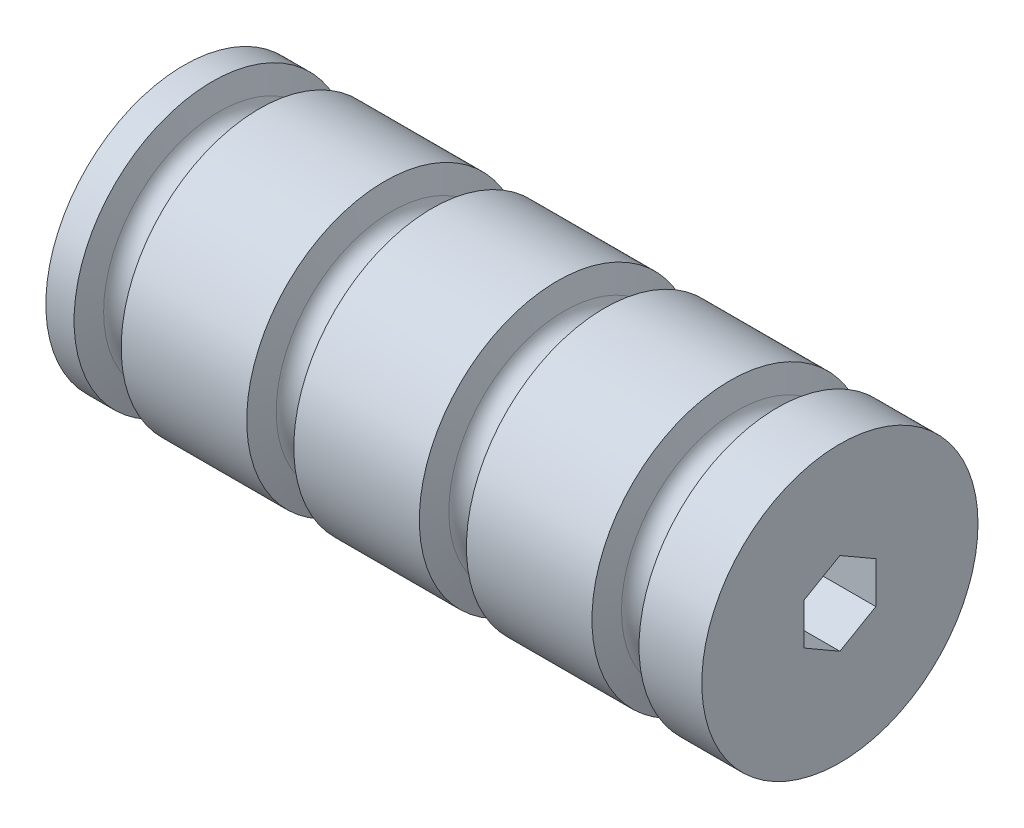
SolidWorks part; units mm, degrees
ref_plane "Front" through (0, 0, 0) normal (0, 0, 1) x (1, 0, 0)
ref_plane "Top" through (0, 0, 0) normal (0, 1, 0) x (1, 0, 0)
ref_plane "Right" through (0, 0, 0) normal (1, 0, 0) x (0, 0, -1)
sketch "Sketch1" plane through (0, 0, 0) normal (0, 0, 1) x (1, 0, 0)
  line L0 (0, 0) -> (0, 25.4)
  line L1 (0, 25.4) -> (120.65, 25.4)
  line L4 (120.65, 25.4) -> (120.65, 0)
  line L5 (120.65, 0) -> (0, 0)
  line L6 (0, 0) -> (-12.0952, 0) construction
  dimension "D1" = 50.8
  dimension "D2" = 120.65
revolve "Revolve1" add sketch "Sketch1" angle 360 about L6
sketch "Sketch2" plane through (0, 0, 0) normal (0, 0, 1) x (1, 0, 0)
  line L0 (5.1948, 25.4) -> (6.4969, 21.2703)
  line L1 (120.65, 25.4) -> (0, 25.4) construction
  line L2 (12.5531, 21.2703) -> (13.8552, 25.4)
  line L3 (13.8552, 25.4) -> (5.1948, 25.4)
  line L4 (36.9448, 25.4) -> (38.2469, 21.2703)
  line L5 (44.3031, 21.2703) -> (45.6052, 25.4)
  line L6 (45.6052, 25.4) -> (36.9448, 25.4)
  line L7 (68.6948, 25.4) -> (69.9969, 21.2703)
  line L8 (76.0531, 21.2703) -> (77.3552, 25.4)
  line L9 (77.3552, 25.4) -> (68.6948, 25.4)
  line L10 (100.4448, 25.4) -> (101.7469, 21.2703)
  line L11 (107.8031, 21.2703) -> (109.1052, 25.4)
  line L12 (109.1052, 25.4) -> (100.4448, 25.4)
  line L13 (0, 25.4) -> (0, -25.4) construction
  line L14 (0, 0) -> (-12.9031, 0) construction
  line L16 (9.525, 22.225) -> (41.275, 22.225) construction
  line L17 (104.775, 22.225) -> (136.525, 22.225) construction
  line L18 (120.65, -25.4) -> (120.65, 25.4) construction
  arc A0 (6.4969, 21.2703) -> (12.5531, 21.2703) centre (9.525, 22.225) ccw
  arc A1 (38.2469, 21.2703) -> (44.3031, 21.2703) centre (41.275, 22.225) ccw
  arc A2 (69.9969, 21.2703) -> (76.0531, 21.2703) centre (73.025, 22.225) ccw
  arc A3 (101.7469, 21.2703) -> (107.8031, 21.2703) centre (104.775, 22.225) ccw
  point P26 (120.65, 22.225)
  dimension "D4" = 3.175
  dimension "D6" = 6.35
  dimension "D3" = 9.525
  dimension "D5" = 35
  dimension "D1" = 4
revolve "Cut-Revolve1" cut sketch "Sketch2" angle 360 about L14
sketch "Sketch3" plane through (0, 0, 0) normal (-1, 0, 0) x (0, 0, 1)
  line L1 (0, 7.6256) -> (-6.604, 3.8128)
  line L2 (-6.604, 3.8128) -> (-6.604, -3.8128)
  line L3 (-6.604, -3.8128) -> (0, -7.6256)
  line L4 (0, -7.6256) -> (6.604, -3.8128)
  line L5 (6.604, -3.8128) -> (6.604, 3.8128)
  line L6 (6.604, 3.8128) -> (0, 7.6256)
  circle A0 centre (0, 0) radius 6.604 construction
  dimension "D1" = 13.208
extrude "Cut-Extrude1" cut sketch "Sketch3" against normal through all
